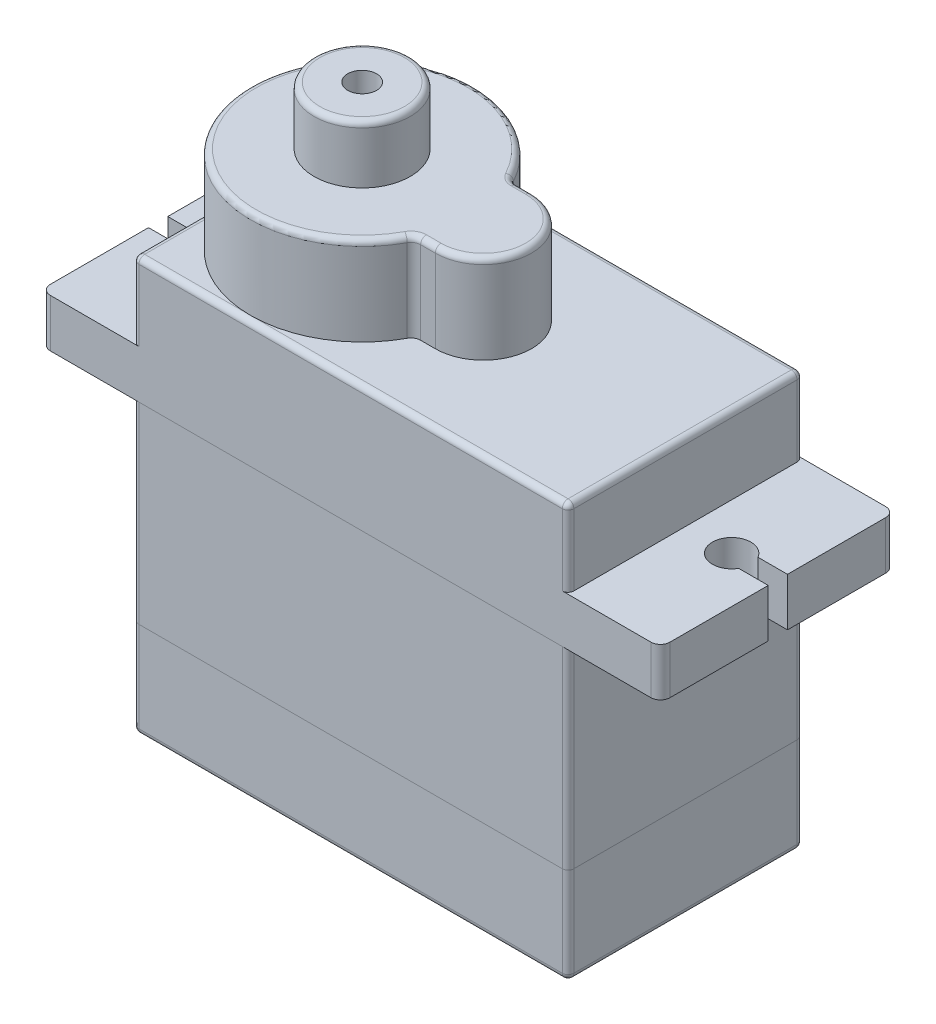
SolidWorks part; units mm, degrees
ref_plane "Front Plane" through (0, 0, 0) normal (0, 0, 1) x (1, 0, 0)
ref_plane "Top Plane" through (0, 0, 0) normal (0, 1, 0) x (1, 0, 0)
ref_plane "Right Plane" through (0, 0, 0) normal (1, 0, 0) x (0, 0, -1)
sketch "Sketch2" plane through (0, 0, 0) normal (0, 1, 0) x (1, 0, 0)
  line L1 (0, 0) -> (22.6, 0)
  line L2 (0, 0) -> (0, 12.2)
  line L3 (0, 12.2) -> (22.6, 12.2)
  line L4 (22.6, 0) -> (22.6, 12.2)
  dimension "D1" = 22.6
  dimension "D2" = 12.2
extrude "Boss-Extrude1" add sketch "Sketch2" along normal blind 5
shell "Shell3" thickness 1 removed face at (11.3, 5, -6.1)
sketch "Sketch5" plane through (0, 5, 0) normal (0, 1, 0) x (1, 0, 0)
  line L1 (1, 1) -> (21.6, 1)
  line L2 (1, 1) -> (1, 11.2)
  line L3 (1, 11.2) -> (21.6, 11.2)
  line L4 (0, 12.2) -> (0, 0)
  line L5 (0, 0) -> (22.6, 0)
  line L6 (22.6, 0) -> (22.6, 12.2)
  line L7 (22.6, 12.2) -> (0, 12.2)
  line L8 (0, 12.2) -> (0, 0)
  line L9 (0, 0) -> (22.6, 0)
  line L10 (22.6, 0) -> (22.6, 12.2)
  line L11 (22.6, 12.2) -> (0, 12.2)
  line L12 (21.6, 1) -> (21.6, 11.2)
  dimension "D1" = 0
extrude "Boss-Extrude2" add sketch "Sketch5" along normal blind 10 separate body
sketch "Sketch6" plane through (0, 15, 0) normal (0, 1, 0) x (1, 0, 0)
  line L4 (22.6, 12.2) -> (0, 12.2)
  line L5 (0, 12.2) -> (0, 0)
  line L6 (0, 0) -> (22.6, 0)
  line L7 (22.6, 0) -> (22.6, 12.2)
  line L8 (22.6, 12.2) -> (0, 12.2)
  line L9 (0, 12.2) -> (0, 0)
  line L10 (0, 0) -> (22.6, 0)
  line L11 (22.6, 0) -> (22.6, 12.2)
  dimension "D1" = 0
extrude "Boss-Extrude3" add sketch "Sketch6" along normal blind 6.5 separate body
sketch "Sketch7" plane through (22.6, 0, 0) normal (1, 0, 0) x (0, 0, -1)
  line L0 (12.2, 21.5) -> (12.2, 15) construction
  line L1 (0, 15) -> (12.2, 15)
  line L2 (0, 15) -> (0, 17.5)
  line L3 (0, 17.5) -> (12.2, 17.5)
  line L4 (12.2, 15) -> (12.2, 17.5)
  dimension "D1" = 2.5
extrude "Boss-Extrude4" add sketch "Sketch7" along normal blind 4.8
sketch "Sketch8" plane through (0, 17.5, 0) normal (0, 1, 0) x (1, 0, 0)
  line L0 (27.4, 6.1) -> (22.6, 6.1) construction
  line L1 (27.4, 12.2) -> (27.4, 0) construction
  line L2 (22.6, 12.2) -> (22.6, 0) construction
  line L3 (25.866, 6.6) -> (27.4, 6.6)
  line L4 (25.866, 5.6) -> (27.4, 5.6)
  circle A0 centre (25, 6.1) radius 1
  line M6 (27.4, 0) -> (27.4, 12.2)
  dimension "D1" = 2
  dimension "D2" = 1
extrude "Cut-Extrude1" cut sketch "Sketch8" against normal blind 4.8 contours L0 A0 | A0 L0 | L0 L3 A0 M6 | L0 A0 L4 M6 region at (26.6778, 17.5, -5.8462) region at (26.6778, 17.5, -6.3538) region at (25, 17.5, -5.6756) region at (25, 17.5, -6.5244)
ref_plane "Plane1" through (11.3, 0, 0) normal (1, 0, 0) x (0, 0, -1)
mirror "Mirror1" about plane through (11.3, 0, 0) normal (1, 0, 0) of "Boss-Extrude4"
mirror "Mirror2" about plane through (11.3, 0, 0) normal (1, 0, 0) of "Cut-Extrude1"
shell "Shell5" thickness 1 removed face at (11.3, 15, -6.1)
sketch "Sketch9" plane through (0, 21.5, 0) normal (0, 1, 0) x (1, 0, 0)
  line L0 (0, 6.1) -> (22.6, 6.1) construction
  line L1 (0, 12.2) -> (0, 0) construction
  line L2 (22.6, 0) -> (22.6, 12.2) construction
  line L3 (14.6, 8.7405) -> (14.6, 3.6809) construction
  line L4 (12.1, 8.6) -> (11.0335, 8.6)
  line L5 (12.1, 3.6) -> (11.0335, 3.6)
  circle A0 centre (5.8, 6.1) radius 5.8
  circle A1 centre (12.1, 6.1) radius 2.5
  dimension "D1" = 11.6
  dimension "D2" = 14.6
  dimension "D3" = 5
extrude "Boss-Extrude5" add sketch "Sketch9" along normal blind 4.6 contours A1 A0 | A0 A1 | A0 A1 | A1 L4 A0 | A1 A0 L5 region at (11.3328, 21.5, -8.5401) region at (12.8089, 21.5, -6.1) region at (5.4782, 21.5, -6.1) region at (10.6798, 21.5, -6.1) region at (11.3328, 21.5, -3.6599)
sketch "Sketch10" plane through (0, 26.1, 0) normal (0, 1, 0) x (1, 0, 0)
  circle A0 centre (5.8, 6.1) radius 2.5
  dimension "D1" = 5
extrude "Boss-Extrude6" add sketch "Sketch10" along normal blind 3 separate body
fillet "Fillet1" radius 0.5 2 edges at (11.0335, 23.8, -8.6) (11.0335, 23.8, -3.6)
sketch "Sketch12" plane through (0, 20.5, 0) normal (0, -1, 0) x (1, 0, 0)
  line L0 (11.3399, -7.6) -> (12.1, -7.6)
  line L1 (12.1, -4.6) -> (11.3399, -4.6)
  line L2 (12.1, -3.6) -> (11.3399, -3.6)
  line L3 (11.3399, -8.6) -> (12.1, -8.6)
  line L4 (12.1, -3.6) -> (11.3399, -3.6)
  line L5 (11.3399, -8.6) -> (12.1, -8.6)
  arc A0 (10.0208, -3.8143) -> (10.0208, -8.3857) centre (5.8, -6.1) ccw
  arc A1 (11.3399, -7.6) -> (10.0208, -8.3857) centre (11.3399, -9.1) ccw
  arc A2 (12.1, -7.6) -> (12.1, -4.6) centre (12.1, -6.1) ccw
  arc A3 (10.0208, -3.8143) -> (11.3399, -4.6) centre (11.3399, -3.1) ccw
  arc A4 (12.1, -8.6) -> (12.1, -3.6) centre (12.1, -6.1) ccw
  arc A5 (11.3399, -8.6) -> (10.9002, -8.8619) centre (11.3399, -9.1) ccw
  arc A6 (10.9002, -3.3381) -> (10.9002, -8.8619) centre (5.8, -6.1) ccw
  arc A7 (10.9002, -3.3381) -> (11.3399, -3.6) centre (11.3399, -3.1) ccw
  arc A8 (12.1, -8.6) -> (12.1, -3.6) centre (12.1, -6.1) ccw
  arc A9 (11.3399, -8.6) -> (10.9002, -8.8619) centre (11.3399, -9.1) ccw
  arc A10 (10.9002, -3.3381) -> (10.9002, -8.8619) centre (5.8, -6.1) ccw
  arc A11 (10.9002, -3.3381) -> (11.3399, -3.6) centre (11.3399, -3.1) ccw
  dimension "D1" = 0
  dimension "D2" = 1
extrude "Cut-Extrude2" cut sketch "Sketch12" against normal blind 4 and the other way up to surface (4 mm away) contours A3 A0 A1 L0 A2 L1 region at (6.4432, 20.5, -6.1) other way up to face at (-2.1654, 16.5, -6.1)
sketch "Sketch13" plane through (0, 0, 0) normal (-1, 0, 0) x (0, 0, 1)
  line L0 (-12.2, 5) -> (0, 5) construction
  line L1 (-8.1, 5) -> (-4.1, 5)
  line L2 (-8.1, 5) -> (-8.1, 4)
  line L3 (-8.1, 4) -> (-4.1, 4)
  line L4 (-4.1, 5) -> (-4.1, 4)
  point P6 (-6.1, 5)
  point P7 (-6.1, 5)
  dimension "D1" = 4
  dimension "D2" = 1
extrude "Cut-Extrude3" cut sketch "Sketch13" against normal blind 4
sketch "Sketch14" plane through (0, 0, 0) normal (-1, 0, 0) x (0, 0, 1)
  line L0 (-8.1, 4.5) -> (-4.1, 4.5) construction
  line L1 (-8.1, 5) -> (-8.1, 4) construction
  line L2 (-4.1, 4) -> (-4.1, 5) construction
  circle A0 centre (-7.5, 4.5) radius 0.5
  circle A1 centre (-6.1, 4.5) radius 0.5
  circle A2 centre (-4.7, 4.5) radius 0.5
  dimension "D1" = 1
  dimension "D3" = 0.6
  dimension "D2" = 3
extrude "Boss-Extrude7" add sketch "Sketch14" along normal blind 1 and the other way blind 1 separate body
fillet "Fillet2" radius 0.3 4 edges at (0, 10, -12.2) (22.6, 10, -12.2) (22.6, 10, 0) (0, 10, 0)
fillet "Fillet3" radius 0.3 8 edges at (11.3, 0, 0) (22.6, 0, -6.1) (11.3, 0, -12.2) (0, 0, -6.1) (0, 2.5, -12.2) (22.6, 2.5, -12.2) (22.6, 2.5, 0) (0, 2.5, 0)
fillet "Fillet4" radius 0.3 9 edges at (0, 21.5, -9.15) (0, 21.5, -3.05) (11.3, 21.5, -12.2) (22.6, 21.5, -6.1) (11.3, 21.5, 0) (0, 19.5, -12.2) (22.6, 19.5, -12.2) (22.6, 19.5, 0) (0, 19.5, 0)
fillet "Fillet5" radius 0.5 4 edges at (-4.8, 16.25, -12.2) (27.4, 16.25, -12.2) (27.4, 16.25, 0) (-4.8, 16.25, 0)
fillet "Fillet6" radius 0.3 6 edges at (11.084, 26.1, -3.5296) (0, 26.1, -6.1) (11.084, 26.1, -8.6704) (11.7199, 26.1, -8.6) (14.6, 26.1, -6.1) (11.7199, 26.1, -3.6)
fillet "Fillet7" radius 0.3 1 edges at (5.8, 29.1, -3.6)
sketch "Sketch15" plane through (0, 29.1, 0) normal (0, 1, 0) x (1, 0, 0)
  circle A0 centre (5.8, 6.1) radius 0.75
  dimension "D1" = 1.5
extrude "Cut-Extrude4" cut sketch "Sketch15" against normal blind 2
